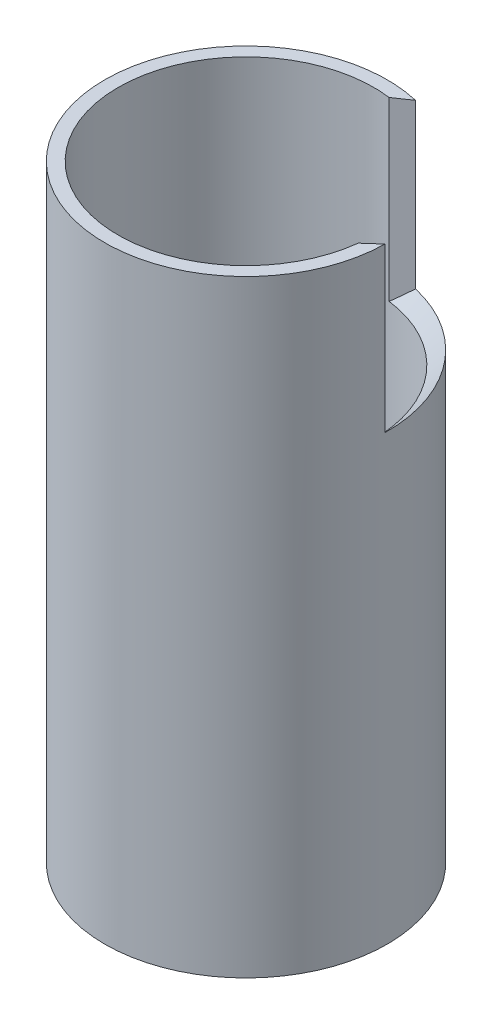
SolidWorks part; units mm, degrees
ref_plane "Front Plane" through (0, 0, 0) normal (0, 0, 1) x (1, 0, 0)
ref_plane "Top Plane" through (0, 0, 0) normal (0, 1, 0) x (1, 0, 0)
ref_plane "Right Plane" through (0, 0, 0) normal (1, 0, 0) x (0, 0, -1)
sketch "Sketch1" plane through (0, 0, 0) normal (0, 1, 0) x (1, 0, 0)
  line L0 (-221.1713, 0) -> (221.1713, 0) construction
  line L1 (0, -168.4638) -> (0, 168.4638) construction
  circle A0 centre (0, 0) radius 76.2
  circle A1 centre (0, 0) radius 84.1375
  point P4 (0, 0)
  point P8 (0, 0)
  dimension "D1" = 152.4
  dimension "D2" = 168.275
extrude "Boss-Extrude1" add sketch "Sketch1" along normal mid plane 361.95
sketch "Sketch2" plane through (0, 180.975, 0) normal (0, 1, 0) x (1, 0, 0)
  line L0 (-172.9245, 0) -> (172.9245, 0) construction
  line L1 (0, -153.4355) -> (0, 153.4355) construction
  line L2 (0, 0) -> (84.1375, 0)
  line L3 (0, 0) -> (20.3547, 81.6383)
  arc A0 (84.1375, 0) -> (20.3547, 81.6383) centre (0, 0) ccw
  point P5 (0, 0)
  point P10 (0, 0)
  dimension "D1" = 76
  dimension "D2" = 90
extrude "Cut-Extrude1" cut sketch "Sketch2" against normal blind 95.25
chamfer "Chamfer1" distance 10 angle 45 2 edges at (66.3013, 85.725, -51.8002) (60.0464, 85.725, -46.9134)
chamfer "Chamfer2" distance 10 angle 45 2 edges at (76.2, 128.35, 0) (18.4344, 128.35, -73.9365)
